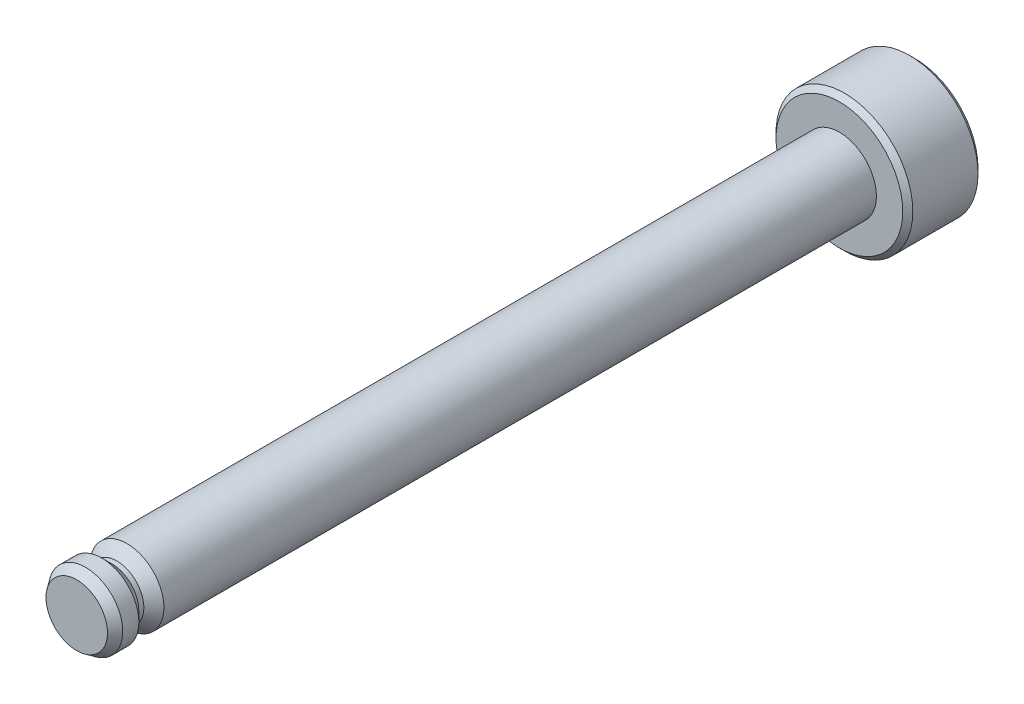
SolidWorks part; units mm, degrees
ref_plane "Front" through (0, 0, 0) normal (0, 0, 1) x (1, 0, 0)
ref_plane "Top" through (0, 0, 0) normal (0, 1, 0) x (1, 0, 0)
ref_plane "Right" through (0, 0, 0) normal (1, 0, 0) x (0, 0, -1)
sketch "Sketch2" plane through (0, 0, 0) normal (0, 0, 1) x (1, 0, 0)
  circle A0 centre (0, 0) radius 1.475
  dimension "D1" = 2.95
extrude "Shaft" add sketch "Sketch2" along normal blind 30.4
sketch "Sketch5" plane through (0, 0, 0) normal (0, 0, 1) x (1, 0, 0)
  circle A0 centre (0, 0) radius 2.725
  dimension "D1" = 5.45
extrude "Head" add sketch "Sketch5" against normal blind 3
chamfer "Chamfer1" distance 0.25 angle 55 1 edges at (1.475, 0, 30.4) first distance on face at (1.475, 0, 30.4)
chamfer "Deburs" distance 0.2 angle 45 2 edges at (2.725, 0, 0) (2.725, 0, -3)
sketch "Sketch6" plane through (0, 0, 0) normal (1, 0, 0) x (0, 0, -1)
  line L0 (0, 0) -> (-28.9, 0) construction
  line L1 (-28.9, 0) -> (-28.9, 1.075) construction
  line L2 (0, 1.475) -> (-30.043, 1.475) construction
  line L3 (-29.4, 1.475) -> (-28.4, 1.475)
  line L4 (-28.4, 1.475) -> (-28.8, 1.075)
  line L5 (-28.8, 1.075) -> (-29, 1.075)
  line L6 (-29, 1.075) -> (-29.4, 1.475)
  line L7 (-28.9, 1.075) -> (-28.9, 1.475) construction
  dimension "D1" = 28.9
  dimension "D2" = 0.4
  dimension "D3" = 1
revolve "e-Clip Notch Long" cut sketch "Sketch6" angle 360 about L0
equation "\"D1@Sketch2\"=\"Plastic Hardware OD@Box Assy.Assembly\""
equation "\"D1@Sketch5\"=\"Hardware Head Countersink Diameter@Box Assy.Assembly\"-.3mm"
equation "\"D1@Head\"=\"Countersink Depth@Box Assy.Assembly\""
equation "\"Length\"= 30mm"
equation "\"D1@Shaft\"=\"Length\"+.4mm"
equation "\"D1@Sketch6\"=\"Length\"-1.1mm"
